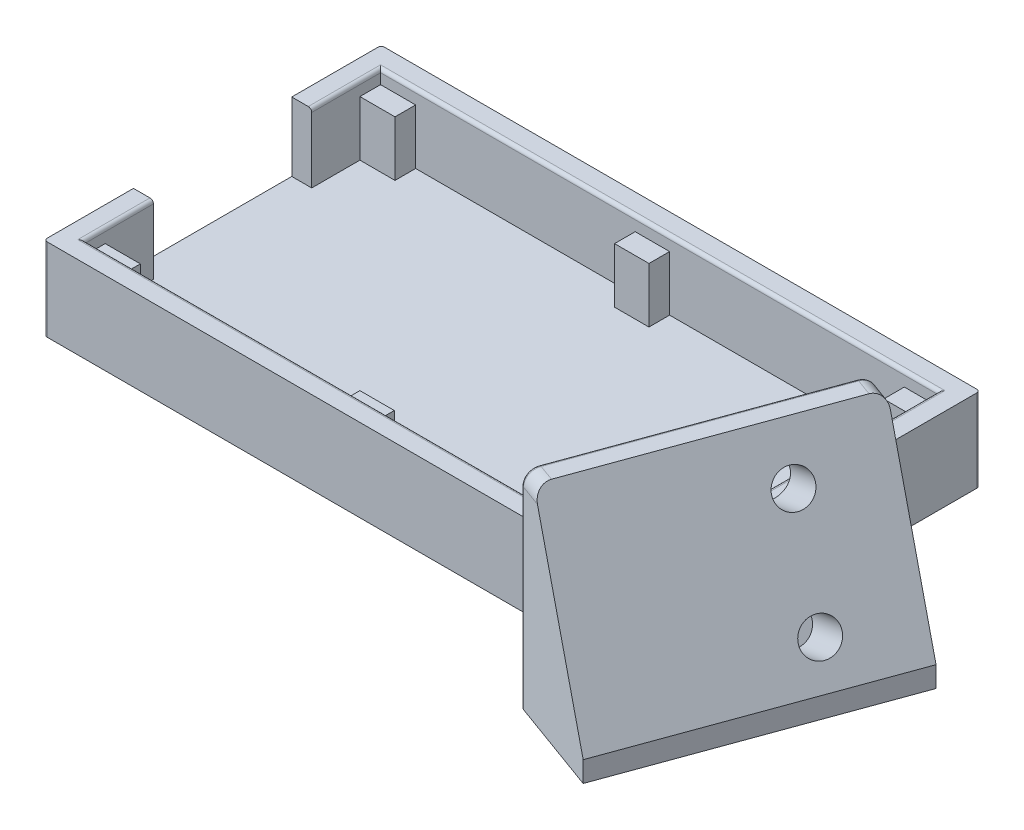
SolidWorks part; units mm, degrees
ref_plane "Front Plane" through (0, 0, 0) normal (0, 0, 1) x (1, 0, 0)
ref_plane "Top Plane" through (0, 0, 0) normal (0, 1, 0) x (1, 0, 0)
ref_plane "Right Plane" through (0, 0, 0) normal (1, 0, 0) x (0, 0, -1)
sketch "Sketch1" plane through (0, 0, 0) normal (0, 1, 0) x (1, 0, 0)
  line L0 (8, 46) -> (39.9, 46)
  line L1 (0, 0) -> (87, 0)
  line L2 (0, 0) -> (0, 49)
  line L3 (0, 49) -> (87, 49)
  line L4 (87, 0) -> (87, 49)
  line L5 (8, 3) -> (39.9, 3)
  line L6 (0, 36) -> (2.9, 36)
  line L7 (2.9, 36) -> (2.9, 43)
  line L8 (2.9, 6) -> (2.9, 13)
  line L9 (2.9, 13) -> (0, 13)
  line L10 (83.9, 43) -> (83.9, 6)
  line L11 (87, 10) -> (99.0208, -2.0208)
  line L12 (77, 0) -> (89.0208, -12.0208)
  line L13 (89.0208, -12.0208) -> (99.0208, -2.0208)
  line L14 (39.9, 46) -> (39.9, 43)
  line L15 (39.9, 43) -> (44.9, 43)
  line L16 (44.9, 43) -> (44.9, 46)
  line L17 (44.9, 46) -> (79, 46)
  line L18 (39.9, 3) -> (39.9, 6)
  line L19 (39.9, 6) -> (44.9, 6)
  line L20 (44.9, 6) -> (44.9, 3)
  line L21 (44.9, 3) -> (79, 3)
  line L22 (79, 3) -> (79, 6)
  line L23 (79, 6) -> (83.9, 6)
  line L24 (79, 46) -> (79, 43)
  line L25 (79, 43) -> (83.9, 43)
  line L26 (8, 46) -> (8, 43)
  line L27 (8, 43) -> (2.9, 43)
  line L28 (8, 3) -> (8, 6)
  line L29 (8, 6) -> (2.9, 6)
sketch "Sketch2" plane through (0, 0, 0) normal (0, 0, 1) x (1, 0, 0)
  line L0 (90, 0) -> (105, 0)
  line L1 (105, 0) -> (105, 3)
  line L2 (105, 3) -> (93, 30)
  line L3 (93, 30) -> (90, 30)
  line L4 (90, 30) -> (90, 0)
extrude "Boss-Extrude1" add sketch "Sketch2" along normal blind 40
move or copy body "Body-Move/Copy1" bodies to move or copy 101 copy no rotation origin (95, 0, 20) rotation axis (0, -1, 0) rotation angle 20
move or copy body "Body-Move/Copy2" bodies to move or copy 102 copy no translate (-2, 0, -25) parameters "D1"=2, "D2"=0, "D3"=25
extrude "Boss-Extrude2" add sketch "Sketch1" along normal blind 2 contours L0 L10 L5 L8 L9 L2 L1 L4 L3 L6 L7 | L10 L0 L7 L6 L2 L9 L8 L5 | L12 L13 L11 L4 L1 region at (7.0015, 0, -44.5) region at (42.6122, 0, -24.5) region at (89.151, 0, 2.151)
extrude "Boss-Extrude3" add sketch "Sketch1<4>" along normal blind 12 contours L0 L10 L5 L8 L9 L2 L1 L4 L3 L6 L7 region at (7.0015, 0, -44.5)
sketch "Sketch1<4>" plane through (0, 0, 0) normal (0, 1, 0) x (1, 0, 0) same geometry as "Sketch1"
sketch "Sketch4" plane through (76.1266, 36.0054, 27.7078) normal (0.8587, 0.4061, 0.3125) x (0.2995, 0.0972, -0.9491)
  line L0 (12.5691, -37.6699) -> (40.4101, -40.6495) construction
  line L1 (12.5691, -37.6699) -> (52.342, -41.9264) construction
  line L2 (50.153, -41.6922) -> (52.7649, -17.2866) construction
  line L3 (40.4101, -40.6495) -> (41.0486, -34.6835) construction
  line L4 (41.0486, -34.6835) -> (42.7448, -18.834) construction
  circle A1 centre (42.7448, -18.834) radius 2.5
  circle A2 centre (41.0486, -34.6835) radius 2.5
extrude "Cut-Extrude2" cut sketch "Sketch4" against normal blind 8
fillet "Fillet1" radius 2 2 edges at (96.5515, 30, -24.9909) (82.8707, 30, 12.5968)
sketch "Sketch10" plane through (0, 12, 0) normal (0, 1, 0) x (1, 0, 0)
  line L5 (83.9, 6) -> (79, 6)
  line L11 (39.9, 3) -> (45, 3)
  line L12 (39.9, 3) -> (39.9, 6)
  line L13 (39.9, 6) -> (45, 6)
  line L14 (45, 3) -> (45, 6)
  line L15 (39.9, 46) -> (44.9, 46)
  line L16 (39.9, 46) -> (39.9, 43)
  line L17 (39.9, 43) -> (44.9, 43)
  line L18 (44.9, 46) -> (44.9, 43)
  line L32 (83.9, 6) -> (83.9, 3)
  line L33 (83.9, 3) -> (79, 3)
  line L39 (79, 6) -> (79, 3)
  line L40 (83.9, 43) -> (79, 43)
  line L41 (83.9, 43) -> (83.9, 46)
  line L42 (83.9, 46) -> (79, 46)
  line L43 (79, 43) -> (79, 46)
  line L44 (8, 46) -> (2.9, 46)
  line L45 (8, 46) -> (8, 43)
  line L46 (8, 43) -> (2.9, 43)
  line L47 (2.9, 46) -> (2.9, 43)
  line L48 (8, 3) -> (2.9, 3)
  line L49 (8, 3) -> (8, 6)
  line L50 (8, 6) -> (2.9, 6)
  line L51 (2.9, 3) -> (2.9, 6)
extrude "Cut-Extrude4" cut sketch "Sketch10" against normal blind 2
fillet "Fillet2" radius 0.5 13 edges at (2.9, 12, -8) (2.9, 12, -41) (0, 6, 0) (87, 6, -49) (0, 6, -49) (94.9416, 29.4142, -24.9535) (88.3015, 30, -6.7101) (81.6615, 29.4142, 11.5333) (95.1419, 14, -25.504) (81.4611, 14, 12.0838) (43.4, 12, -3) (83.9, 12, -24.5) (43.4, 12, -46)
